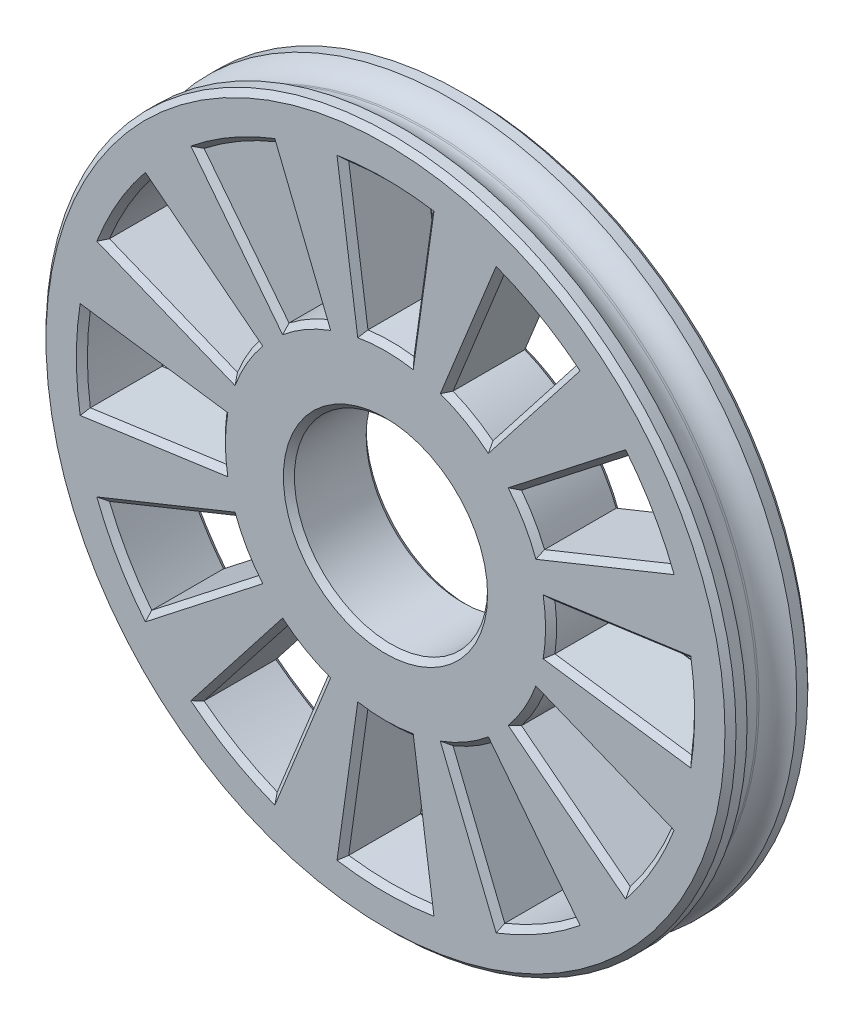
SolidWorks part; units mm, degrees
ref_plane "Front Plane" through (0, 0, 0) normal (0, 0, 1) x (1, 0, 0)
ref_plane "Top Plane" through (0, 0, 0) normal (0, 1, 0) x (1, 0, 0)
ref_plane "Right Plane" through (0, 0, 0) normal (1, 0, 0) x (0, 0, -1)
sketch "Sketch1" plane through (0, 0, 0) normal (0, 0, 1) x (1, 0, 0)
  circle A0 centre (0, 0) radius 12.5
  dimension "D1" = 25
extrude "Boss-Extrude1" add sketch "Sketch1" along normal blind 0.6
sketch "Sketch2" plane through (0, 0, 0.6) normal (0, 0, 1) x (1, 0, 0)
  circle A2 centre (0, 0) radius 12
  circle A3 centre (0, 0) radius 12
  dimension "D1" = 0.5
extrude "Boss-Extrude2" add sketch "Sketch2" along normal blind 1.8
sketch "Sketch3" plane through (0, 0, 2.4) normal (0, 0, 1) x (1, 0, 0)
  circle A2 centre (0, 0) radius 12.5
  circle A3 centre (0, 0) radius 12.5
  dimension "D1" = 0.5
extrude "Boss-Extrude3" add sketch "Sketch3" along normal blind 0.6
sketch "Sketch4" plane through (0, 0, 3) normal (0, 0, 1) x (1, 0, 0)
  circle A0 centre (0, 0) radius 3.5
  dimension "D1" = 7
extrude "Cut-Extrude1" cut sketch "Sketch4" against normal blind 10
fillet "Fillet1" radius 1 2 edges at (12, 0, 0.6) (12, 0, 2.4)
sketch "Sketch6" plane through (0, 0, 3) normal (0, 0, 1) x (1, 0, 0)
  line L0 (0, 0) -> (-13.4054, 0) construction
  line L1 (0, 0) -> (-14.1068, -1.9826)
  line L2 (0, 0) -> (-13.2989, 1.869)
  line L3 (0, 0) -> (-10.5827, 8.2681)
  line L4 (0, 0) -> (-13.2081, 5.3364)
  line L5 (0, 0) -> (-5.0308, 12.4517)
  line L6 (0, 0) -> (-8.7704, 11.2255)
  line L7 (0, 0) -> (1.869, 13.2989)
  line L8 (0, 0) -> (-1.9826, 14.1068)
  line L9 (0, 0) -> (8.2681, 10.5827)
  line L10 (0, 0) -> (5.3364, 13.2081)
  line L11 (0, 0) -> (12.4517, 5.0308)
  line L12 (0, 0) -> (11.2255, 8.7704)
  line L13 (0, 0) -> (13.2989, -1.869)
  line L14 (0, 0) -> (14.1068, 1.9826)
  line L15 (0, 0) -> (10.5827, -8.2681)
  line L16 (0, 0) -> (13.2081, -5.3364)
  line L17 (0, 0) -> (5.0308, -12.4517)
  line L18 (0, 0) -> (8.7704, -11.2255)
  line L19 (0, 0) -> (-1.869, -13.2989)
  line L20 (0, 0) -> (1.9826, -14.1068)
  line L21 (0, 0) -> (-8.2681, -10.5827)
  line L22 (0, 0) -> (-5.3364, -13.2081)
  line L23 (0, 0) -> (-12.4517, -5.0308)
  line L24 (0, 0) -> (-11.2255, -8.7704)
  circle A1 centre (0, 0) radius 6
  circle A2 centre (0, 0) radius 11
  circle A3 centre (0, 0) radius 11
  point P29 (0, 0)
  dimension "D1" = 8
  dimension "D2" = 8
  dimension "D3" = 1.5
  dimension "D4" = 5
  dimension "D5" = 12
extrude "Cut-Extrude2" cut sketch "Sketch6" against normal blind 5 contours A1 L0 A3 L1 | L0 A1 L2 A3 | L3 A3 L4 A1 | L5 A3 L6 A1 | L7 A3 L8 A1 | L9 A3 L10 A1 | L11 A3 L12 A1 | L13 A3 L14 A1 | L15 A3 L16 A1 | L17 A3 L18 A1 | L19 A3 L20 A1 | L21 A3 L22 A1 | L23 A3 L24 A1
chamfer "倒角1" distance 0.2 angle 45 100 edges at (-11, 0, 3) (-8.4173, -1.183, 3) (-6, 0, 3) (-8.4173, 1.183, 3) (12.5, 0, 3) (3.5, 0, 3) (-5.5, -9.5263, 3) (-3.1842, -7.8811, 3) (-3, -5.1962, 3) (-5.2331, -6.6981, 3) (-9.5263, -5.5, 3) (-6.6981, -5.2331, 3) (-5.1962, -3, 3) (-7.8811, -3.1842, 3) (0, -11, 3) (1.183, -8.4173, 3) (0, -6, 3) (-1.183, -8.4173, 3) (9.5263, -5.5, 3) (7.8811, -3.1842, 3) (5.1962, -3, 3) (6.6981, -5.2331, 3) (5.5, -9.5263, 3) (5.2331, -6.6981, 3) (3, -5.1962, 3) (3.1842, -7.8811, 3) (11, 0, 3) (8.4173, 1.183, 3) (6, 0, 3) (8.4173, -1.183, 3) (5.5, 9.5263, 3) (3.1842, 7.8811, 3) (3, 5.1962, 3) (5.2331, 6.6981, 3) (9.5263, 5.5, 3) (6.6981, 5.2331, 3) (5.1962, 3, 3) (7.8811, 3.1842, 3) (0, 11, 3) (-1.183, 8.4173, 3) (0, 6, 3) (1.183, 8.4173, 3) (-9.5263, 5.5, 3) (-7.8811, 3.1842, 3) (-5.1962, 3, 3) (-6.6981, 5.2331, 3) (-5.5, 9.5263, 3) (-5.2331, 6.6981, 3) (-3, 5.1962, 3) (-3.1842, 7.8811, 3) (-8.4173, -1.183, 0) (-11, 0, 0) (-8.4173, 1.183, 0) (-6, 0, 0) (3.5, 0, 0) (12.5, 0, 0) (-3.1842, -7.8811, 0) (-5.5, -9.5263, 0) (-5.2331, -6.6981, 0) (-3, -5.1962, 0) (-6.6981, -5.2331, 0) (-9.5263, -5.5, 0) (-7.8811, -3.1842, 0) (-5.1962, -3, 0) (1.183, -8.4173, 0) (0, -11, 0) (-1.183, -8.4173, 0) (0, -6, 0) (7.8811, -3.1842, 0) (9.5263, -5.5, 0) (6.6981, -5.2331, 0) (5.1962, -3, 0) (5.2331, -6.6981, 0) (5.5, -9.5263, 0) (3.1842, -7.8811, 0) (3, -5.1962, 0) (8.4173, 1.183, 0) (11, 0, 0) (8.4173, -1.183, 0) (6, 0, 0) (3.1842, 7.8811, 0) (5.5, 9.5263, 0) (5.2331, 6.6981, 0) (3, 5.1962, 0) (6.6981, 5.2331, 0) (9.5263, 5.5, 0) (7.8811, 3.1842, 0) (5.1962, 3, 0) (-1.183, 8.4173, 0) (0, 11, 0) (1.183, 8.4173, 0) (0, 6, 0) (-7.8811, 3.1842, 0) (-9.5263, 5.5, 0) (-6.6981, 5.2331, 0) (-5.1962, 3, 0) (-5.2331, 6.6981, 0) (-5.5, 9.5263, 0) (-3.1842, 7.8811, 0) (-3, 5.1962, 0)
